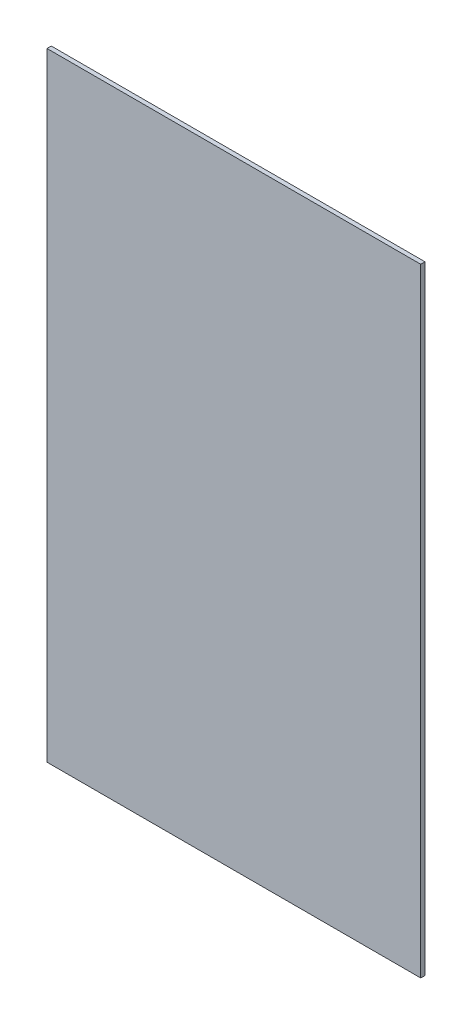
SolidWorks part; units mm, degrees
ref_plane "Спереди" through (0, 0, 0) normal (0, 0, 1) x (1, 0, 0)
ref_plane "Сверху" through (0, 0, 0) normal (0, 1, 0) x (1, 0, 0)
ref_plane "Справа" through (0, 0, 0) normal (1, 0, 0) x (0, 0, -1)
sketch "Эскиз1" plane through (0, 0, 0) normal (0, 0, 1) x (1, 0, 0)
  line L1 (0, 436.3) -> (-524, 436.3)
  line L2 (0, 436.3) -> (0, -430.3)
  line L3 (0, -430.3) -> (-524, -430.3)
  line L4 (-524, 436.3) -> (-524, -430.3)
  line L5 (-524, -436.3) -> (-524, 436.3) construction
  line L6 (-518, -430.3) -> (0, -430.3) construction
  line L7 (0, 436.3) -> (-518, 436.3) construction
  line L8 (0, 54.3) -> (0, 436.3) construction
extrude "Бобышка-Вытянуть1" add sketch "Эскиз1" against normal blind 6
equation "\"Ширина груза\"= 420"
equation "\"Глубина груза\"= 490"
equation "\"Высота груза\"= 297"
equation "\"Ширина ячейки\"= \"Ширина груза\" + 10"
equation "\"Глубина ячейки\"= \"Глубина груза\" + 10"
equation "\"Высота ячейки\"= \"Высота груза\" + 10 + 13"
equation "\"Колво ячеек ширина\"= 2"
equation "\"Колво ячеек высота\"= 2"
equation "\"Толщина стенки\" = 6"
equation "\"Крепление дверцы\"= 5"
equation "\"Ширина рейки\"= \"Толщина шестерни\""
equation "\"Высота рейки\"= 20"
equation "\"Высота пола\"= 20"
equation "\"Колво полозьев\"= 5"
equation "\"Отступ рейки\"= 20"
equation "\"Глубина каретки\"= \"Глубина ячейки\" + 30 + \"Мотор Y высота корпуса\" + 20"
equation "\"Длинна рейки\"= ( \"Ширина ячейки\" + \"Толщина стенки\" + \"Крепление дверцы\" ) * \"Колво ячеек ширина\" + \"Ширина ячейки выгрузки\" * \"Колво выгрузки\" + \"Толщина стенки\""
equation "\"Отступ шпильки\"= 26"
equation "\"Диаметр шпильки\"= 5"
equation "\"Длинна шпильки\"= ( \"Высота ячейки\" + \"Толщина стенки\" + \"Высота пола\" ) * \"Колво ячеек высота\" + ( \"Толщина стенки\" + \"Отступ рейки\" ) * 2 "
equation "\"Ширина пластины\"= 50  "
equation "\"Высота зона выгрузки\"= \"Высота ячейки\" * 2 + \"Толщина стенки\" * 2"
equation "\"Колво выгрузки\"= 1"
equation "\"Ширина ячейки выгрузки\"= \"Ширина ячейки\" + \"Толщина стенки\" + \"Отступ крепления мотора фиксации\"*2"
equation "\"Отступ крепления мотора фиксации\" = 30"
equation "\"Мотор X ширина корпуса\"= 42.3"
equation "\"Мотор X высота корпуса\"= 42.3"
equation "\"Мотор X длина корпуса\"= 40"
equation "\"Мотор X вылет вала\"= 19.8"
equation "\"Мотор Y ширина корпуса\"= 42.3"
equation "\"Мотор Y высота корпуса\"= 42.3"
equation "\"Мотор Y длина корпуса\"= 48"
equation "\"Мотор Y вылет вала\"= 30"
equation "\"Мотор Z ширина корпуса\"= 42"
equation "\"Мотор Z высота корпуса\"= 42"
equation "\"Мотор Z длина корпуса\"= 40"
equation "\"Мотор Z вылет вала\"= 23"
equation "\"Мотор диаметр вала ПРЕДВ\"= 5"
equation "\"Мотор шаг крепления ПРЕДВ\"= 31"
equation "\"Мотор диаметр отверстий ПРЕДВ\"= 3"
equation "\"Мотор глубина отверстий ПРЕДВ\"= 4.5"
equation "\"Мотор диаметр буртика ПРЕДВ\"= 22"
equation "\"Мотор высота буртика ПРЕДВ\"= 2"
equation "\"Мотор диаметр шкива ПРЕДВ\"= 16"
equation "\"Мотор длина шкива ПРЕДВ\"= 12"
equation "\"Мотор отступ шкива ПРЕДВ\"= 5"
equation "\"Мотор X шаг градусов\"= 1.8"
equation "\"Мотор Y шаг градусов\"= 1.8"
equation "\"Мотор Z шаг градусов\"= 1.8"
equation "\"Мотор Y диаметр ротора\"= 25.78"
equation "\"Толщина шестерни\"= 10"
equation "\"D1@Бобышка-Вытянуть1\"=\"Толщина стенки\""
